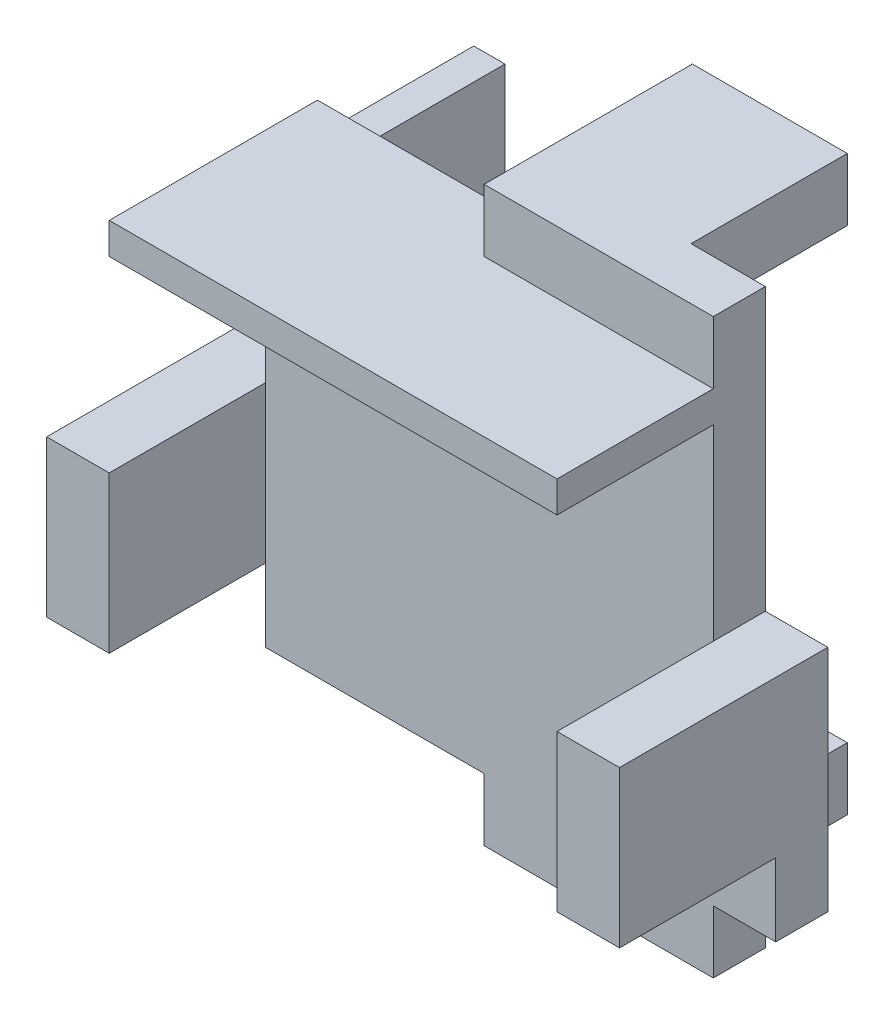
SolidWorks part; units mm, degrees
ref_plane "前视基准面" through (0, 0, 0) normal (0, 0, 1) x (1, 0, 0)
ref_plane "上视基准面" through (0, 0, 0) normal (0, 1, 0) x (1, 0, 0)
ref_plane "右视基准面" through (0, 0, 0) normal (1, 0, 0) x (0, 0, -1)
sketch "草图1" plane through (0, 0, 0) normal (0, 0, 1) x (1, 0, 0)
  line L0 (-50.797, 9.0326) -> (-50.797, 3.0326)
  line L1 (-77.797, 31.0326) -> (-71.797, 31.0326)
  line L2 (-77.797, 31.0326) -> (-77.797, 9.0326)
  line L3 (-77.797, 9.0326) -> (-50.797, 9.0326)
  line L4 (-22.797, 31.0326) -> (-22.797, 9.0326)
  line L5 (-50.797, 58.0326) -> (-28.797, 58.0326)
  line L6 (-50.797, 58.0326) -> (-50.797, 52.0326)
  line L7 (-50.797, 3.0326) -> (-28.797, 3.0326)
  line L8 (-28.797, 58.0326) -> (-28.797, 31.0326)
  line L9 (-28.797, 9.0326) -> (-28.797, 3.0326)
  line L10 (-28.797, 9.0326) -> (-22.797, 9.0326)
  line L11 (-28.797, 31.0326) -> (-22.797, 31.0326)
  line L12 (-50.797, 49.0326) -> (-50.797, 31.0326)
  line L13 (-50.797, 9.0326) -> (-35.797, 9.0326)
  line L14 (-50.797, 9.0326) -> (-50.797, 3.0326)
  line L15 (-50.797, 3.0326) -> (-35.797, 3.0326)
  line L16 (-35.797, 9.0326) -> (-35.797, 3.0326)
  line L17 (-50.797, 52.0326) -> (-35.797, 52.0326)
  line L18 (-50.797, 52.0326) -> (-50.797, 58.0326)
  line L19 (-50.797, 58.0326) -> (-35.797, 58.0326)
  line L20 (-35.797, 52.0326) -> (-35.797, 58.0326)
  line L21 (-28.797, 31.0326) -> (-22.797, 31.0326)
  line L22 (-28.797, 31.0326) -> (-28.797, 16.0326)
  line L23 (-28.797, 16.0326) -> (-22.797, 16.0326)
  line L24 (-22.797, 31.0326) -> (-22.797, 16.0326)
  line L25 (-77.797, 31.0326) -> (-71.797, 31.0326)
  line L26 (-77.797, 31.0326) -> (-77.797, 16.0326)
  line L27 (-77.797, 16.0326) -> (-71.797, 16.0326)
  line L28 (-71.797, 31.0326) -> (-71.797, 16.0326)
  line L29 (-68.797, 9.0326) -> (-71.797, 9.0326)
  line L30 (-68.797, 9.0326) -> (-68.797, 49.0326)
  line L31 (-68.797, 49.0326) -> (-71.797, 49.0326)
  line L32 (-71.797, 9.0326) -> (-71.797, 49.0326)
  line L33 (-28.797, 49.0326) -> (-71.797, 49.0326)
  line L34 (-28.797, 49.0326) -> (-28.797, 52.0326)
  line L35 (-28.797, 52.0326) -> (-71.797, 52.0326)
  line L36 (-71.797, 49.0326) -> (-71.797, 52.0326)
  line L37 (-68.797, 31.0326) -> (-50.797, 31.0326)
  dimension "D1" = 55
  dimension "D2" = 22
  dimension "D3" = 55
  dimension "D4" = 22
  dimension "D5" = 6
  dimension "D6" = 6
  dimension "D7" = 15
  dimension "D8" = 6
  dimension "D9" = 15
  dimension "D10" = 15
  dimension "D11" = 6
  dimension "D12" = 15
  dimension "D13" = 3
  dimension "D14" = 40
extrude "拉伸-薄壁3" add sketch "草图1" along normal blind 15 thin contours L11 thin type one direction wall 15
extrude "凸台-拉伸3" add sketch "草图1<7>" along normal blind 15 separate body contours L28 L1 L2 L27 region at (-74.797, 23.5326, 0)
sketch "草图1<7>" plane through (0, 0, 0) normal (0, 0, 1) x (1, 0, 0) same geometry as "草图1"
extrude "凸台-拉伸4" add sketch "草图1<8>" along normal blind 15 separate body contours L36 L31 L33 L8 L35 L17 region at (-50.297, 50.5326, 0)
sketch "草图1<8>" plane through (0, 0, 0) normal (0, 0, 1) x (1, 0, 0) same geometry as "草图1"
extrude "凸台-拉伸5" add sketch "草图1<11>" against normal blind 5 contours L37 L30 L3 L13 L16 L7 L9 L10 L4 L23 L22 L8 L33 L12 | L30 L37 L12 L33 | L22 L23 L4 L11 | L28 L1 L2 L27 | L32 L3 L30 L31 L28 | L36 L31 L33 L8 L35 L17 | L17 L20 L5 L6 | L35 L8 L5 L20 | L16 L13 L0 L7 region at (-43.297, 6.0326, 0) region at (-44.9565, 25.1922, 0) region at (-70.297, 29.0326, 0) region at (-59.797, 40.0326, 0) region at (-74.797, 23.5326, 0) region at (-50.297, 50.5326, 0) region at (-25.797, 23.5326, 0) region at (-43.297, 55.0326, 0) region at (-32.297, 55.0326, 0)
sketch "草图1<11>" plane through (0, 0, 0) normal (0, 0, 1) x (1, 0, 0) same geometry as "草图1"
extrude "凸台-拉伸10" add sketch "草图1<13>" against normal blind 20 contours L32 L29 L30 L31
sketch "草图1<13>" plane through (0, 0, 0) normal (0, 0, 1) x (1, 0, 0) same geometry as "草图1"
sketch "草图3" plane through (0, 0, -5) normal (0, 0, -1) x (-1, 0, 0)
  line L0 (50.797, 58.0326) -> (28.797, 58.0326) construction
  line L1 (35.9279, 58.0326) -> (50.797, 58.0326)
  line L2 (35.9279, 58.0326) -> (35.9279, 52.0326)
  line L3 (35.9279, 52.0326) -> (50.797, 52.0326)
  line L4 (50.797, 58.0326) -> (50.797, 52.0326)
  line L5 (50.797, 3.0326) -> (28.797, 3.0326) construction
  line L6 (50.797, 9.0326) -> (35.9279, 9.0326)
  line L7 (50.797, 9.0326) -> (50.797, 3.0326)
  line L8 (50.797, 3.0326) -> (35.9279, 3.0326)
  line L9 (35.9279, 9.0326) -> (35.9279, 3.0326)
extrude "凸台-拉伸15" add sketch "草图3" along normal blind 15
